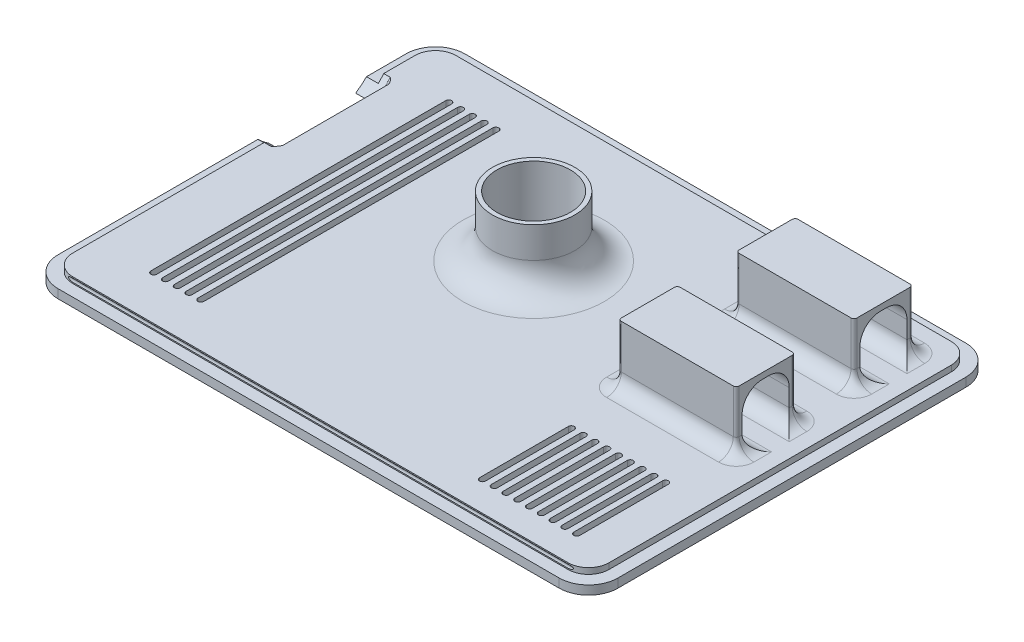
SolidWorks part; units mm, degrees
ref_plane "Front Plane" through (0, 0, 0) normal (0, 0, 1) x (1, 0, 0)
ref_plane "Top Plane" through (0, 0, 0) normal (0, 1, 0) x (1, 0, 0)
ref_plane "Right Plane" through (0, 0, 0) normal (1, 0, 0) x (0, 0, -1)
sketch "Sketch1" plane through (0, 0, 0) normal (0, 1, 0) x (1, 0, 0)
  line L0 (-95.075, -69.075) -> (95.075, -69.075)
  line L7 (95.075, -69.075) -> (95.075, 69.075)
  line L8 (-95.075, 69.075) -> (95.075, 69.075)
  line L9 (-95.075, -69.075) -> (-95.075, 69.075)
  point P0 (0, 69.075)
  point P2 (-95.075, 0)
  dimension "D1" = 138.15
  dimension "D2" = 190.15
extrude "Lid" add sketch "Sketch1" along normal blind 3
sketch "Sketch2" plane through (0, 3, 0) normal (0, 1, 0) x (1, 0, 0)
  line L0 (-91.075, 65.075) -> (-91.075, -65.075)
  line L1 (-91.075, -65.075) -> (91.075, -65.075)
  line L2 (91.075, -65.075) -> (91.075, 65.075)
  line L3 (91.075, 65.075) -> (-91.075, 65.075)
  line L4 (-95.075, 69.075) -> (-95.075, -69.075)
  line L5 (-95.075, -69.075) -> (95.075, -69.075)
  line L6 (95.075, -69.075) -> (95.075, 69.075)
  line L7 (95.075, 69.075) -> (-95.075, 69.075)
  line L8 (-95.075, 69.075) -> (-95.075, -69.075)
  line L9 (-95.075, -69.075) -> (95.075, -69.075)
  line L10 (95.075, -69.075) -> (95.075, 69.075)
  line L11 (95.075, 69.075) -> (-95.075, 69.075)
  dimension "D1" = 0
  dimension "D2" = 4
extrude "Insert" add sketch "Sketch2" along normal blind 2 contours L0 L1 L2 L3
sketch "Sketch3" plane through (0, 5, 0) normal (0, 1, 0) x (1, 0, 0)
  line L1 (41.075, 35.075) -> (81.075, 35.075)
  line L2 (41.075, 35.075) -> (41.075, 55.075)
  line L3 (41.075, 55.075) -> (81.075, 55.075)
  line L4 (91.075, 65.075) -> (-91.075, 65.075)
  line L5 (-91.075, 65.075) -> (-91.075, -65.075)
  line L6 (-91.075, -65.075) -> (91.075, -65.075)
  line L7 (91.075, -65.075) -> (91.075, 65.075)
  line L8 (91.075, 65.075) -> (-91.075, 65.075)
  line L9 (-91.075, 65.075) -> (-91.075, -65.075)
  line L10 (-91.075, -65.075) -> (91.075, -65.075)
  line L11 (91.075, -65.075) -> (91.075, 65.075)
  line L12 (81.075, 35.075) -> (81.075, 55.075)
  line L13 (41.075, 35.075) -> (81.075, 55.075) construction
  line L14 (41.075, 55.075) -> (81.075, 35.075) construction
  line L15 (41.075, 15.075) -> (81.075, 15.075)
  line L16 (41.075, 15.075) -> (41.075, -4.925)
  line L17 (41.075, -4.925) -> (81.075, -4.925)
  line L18 (81.075, 15.075) -> (81.075, -4.925)
  line L19 (41.075, 15.075) -> (81.075, -4.925) construction
  line L20 (41.075, -4.925) -> (81.075, 15.075) construction
  point P2 (61.075, 45.075)
  point P17 (61.075, 5.075)
  dimension "D2" = 10
  dimension "D3" = 50
  dimension "D4" = 10
  dimension "D5" = 30
  dimension "D6" = 50
  dimension "D7" = 70
  dimension "D1" = 0
extrude "Battery Contacts" add sketch "Sketch3" along normal blind 19.9 contours L2 L1 L12 L3 | L16 L15 L18 L17
sketch "Sketch9" plane through (81.075, 0, 0) normal (1, 0, 0) x (0, 0, -1)
  line L0 (-4.925, 5) -> (15.075, 5) construction
  line L1 (53.075, 5) -> (53.075, 15.9)
  line L2 (15.075, 24.9) -> (-4.925, 24.9) construction
  line L3 (53.075, 5) -> (37.075, 5)
  line L4 (35.075, 5) -> (55.075, 5) construction
  line L5 (37.075, 5) -> (37.075, 15.9)
  line L6 (55.075, 24.9) -> (35.075, 24.9) construction
  line L7 (46.075, 22.9) -> (44.075, 22.9)
  line L8 (-4.925, 5) -> (15.075, 5)
  line L9 (15.075, 5) -> (15.075, 24.9)
  line L10 (15.075, 24.9) -> (-4.925, 24.9)
  line L11 (-4.925, 24.9) -> (-4.925, 5)
  line L12 (35.075, 5) -> (55.075, 5)
  line L13 (55.075, 5) -> (55.075, 24.9)
  line L14 (55.075, 24.9) -> (35.075, 24.9)
  line L15 (35.075, 24.9) -> (35.075, 5)
  line L16 (-65.075, 5) -> (65.075, 5) construction
  line L17 (-2.925, 5) -> (13.075, 5)
  line L18 (-2.925, 5) -> (-2.925, 15.9)
  line L19 (4.075, 22.9) -> (6.075, 22.9)
  line L20 (13.075, 5) -> (13.075, 15.9)
  line L21 (25.075, -986.7231) -> (25.075, 49013.2769) construction
  line L22 (53.075, 5) -> (53.075, 15.9)
  arc A0 (-2.925, 15.9) -> (4.075, 22.9) centre (4.075, 15.9) cw
  arc A1 (6.075, 22.9) -> (13.075, 15.9) centre (6.075, 15.9) cw
  arc A2 (53.075, 15.9) -> (46.075, 22.9) centre (46.075, 15.9) ccw
  arc A3 (44.075, 22.9) -> (37.075, 15.9) centre (44.075, 15.9) ccw
  dimension "D1" = 2
  dimension "D2" = 2
  dimension "D3" = 2
  dimension "D4" = 2
  dimension "D5" = 10
extrude "Contact Lighteners" cut sketch "Sketch9" against normal up to next contours A1 L19 A0 L18 L8 L20 | L7 A3 L5 L3 L1 A2 region at (81.075, 13.3646, -45.075) region at (81.075, 13.3646, -5.075)
sketch "Sketch4" plane through (0, 5, 0) normal (0, 1, 0) x (1, 0, 0)
  line L1 (-22.275, 29.625) -> (1.225, 29.625) construction
  line L2 (-22.275, 29.625) -> (-22.275, 6.125) construction
  line L3 (-22.275, 6.125) -> (1.225, 6.125) construction
  line L4 (91.075, 65.075) -> (-91.075, 65.075)
  line L5 (-91.075, 65.075) -> (-91.075, -65.075)
  line L6 (-91.075, -65.075) -> (91.075, -65.075)
  line L7 (91.075, -65.075) -> (91.075, 65.075)
  line L8 (91.075, 65.075) -> (-91.075, 65.075)
  line L9 (-91.075, 65.075) -> (-91.075, -65.075)
  line L10 (-91.075, -65.075) -> (91.075, -65.075)
  line L11 (91.075, -65.075) -> (91.075, 65.075)
  line L12 (1.225, 29.625) -> (1.225, 6.125) construction
  line L13 (-22.275, 29.625) -> (1.225, 6.125) construction
  line L14 (-22.275, 6.125) -> (1.225, 29.625) construction
  line L566 (-10.525, 28.875) -> (-10.525, 6.875) construction
  line L567 (-9.775, 28.875) -> (-9.775, 6.875)
  line L568 (-63.575, 50.075) -> (-63.575, -50.075) construction
  line L569 (-81.075, 50.075) -> (-46.075, 50.075) construction
  line L570 (-81.075, 50.075) -> (-81.075, -50.075) construction
  line L571 (-81.075, -50.075) -> (-46.075, -50.075) construction
  line L572 (-46.075, 50.075) -> (-46.075, -50.075) construction
  line L573 (-62.575, 50.075) -> (-62.575, -50.075)
  line L574 (-64.575, 50.075) -> (-64.575, -50.075)
  line L575 (-59.575, 50.075) -> (-59.575, -50.075) construction
  line L576 (-58.575, 50.075) -> (-58.575, -50.075)
  line L577 (-60.575, 50.075) -> (-60.575, -50.075)
  line L578 (-55.575, 50.075) -> (-55.575, -50.075) construction
  line L579 (-54.575, 50.075) -> (-54.575, -50.075)
  line L580 (-56.575, 50.075) -> (-56.575, -50.075)
  line L581 (-67.575, 50.075) -> (-67.575, -50.075) construction
  line L582 (-11.275, 28.875) -> (-11.275, 6.875)
  line L583 (-7.525, 28.875) -> (-7.525, 6.875) construction
  line L584 (-6.775, 28.875) -> (-6.775, 6.875)
  line L585 (-8.275, 28.875) -> (-8.275, 6.875)
  line L586 (-4.525, 27.9776) -> (-4.525, 7.7724) construction
  line L587 (-3.775, 27.4927) -> (-3.775, 8.2573)
  line L588 (-5.275, 28.3869) -> (-5.275, 7.3631)
  line L589 (-66.575, 50.075) -> (-66.575, -50.075)
  line L590 (-68.575, 50.075) -> (-68.575, -50.075)
  line L591 (-63.575, 50.075) -> (-63.575, -50.075) construction
  line L592 (-62.575, 50.075) -> (-62.575, -50.075)
  line L593 (-64.575, 50.075) -> (-64.575, -50.075)
  line L594 (-71.575, 50.075) -> (-71.575, -50.075) construction
  line L595 (-70.575, 50.075) -> (-70.575, -50.075)
  line L596 (-72.575, 50.075) -> (-72.575, -50.075)
  line L597 (41.075, -4.925) -> (81.075, -4.925) construction
  line L598 (41.075, -55.075) -> (81.075, -55.075) construction
  line L599 (41.075, -55.075) -> (41.075, -24.925) construction
  line L600 (41.075, -24.925) -> (81.075, -24.925) construction
  line L601 (81.075, -55.075) -> (81.075, -24.925) construction
  line L602 (61.075, -24.925) -> (61.075, -55.075) construction
  line L603 (62.075, -24.925) -> (62.075, -55.075)
  line L604 (60.075, -24.925) -> (60.075, -55.075)
  line L605 (65.075, -24.925) -> (65.075, -55.075) construction
  line L606 (66.075, -24.925) -> (66.075, -55.075)
  line L607 (-1.525, 25.429) -> (-1.525, 10.321) construction
  line L608 (-0.775, 24.4324) -> (-0.775, 11.3176)
  line L609 (-2.275, 26.2416) -> (-2.275, 9.5084)
  line L610 (64.075, -24.925) -> (64.075, -55.075)
  line L611 (69.075, -24.925) -> (69.075, -55.075) construction
  line L612 (70.075, -24.925) -> (70.075, -55.075)
  line L613 (68.075, -24.925) -> (68.075, -55.075)
  line L614 (73.075, -24.925) -> (73.075, -55.075) construction
  line L615 (74.075, -24.925) -> (74.075, -55.075)
  line L616 (72.075, -24.925) -> (72.075, -55.075)
  line L617 (77.075, -24.925) -> (77.075, -55.075) construction
  line L618 (78.075, -24.925) -> (78.075, -55.075)
  line L619 (76.075, -24.925) -> (76.075, -55.075)
  line L620 (49.075, -24.925) -> (49.075, -55.075) construction
  line L621 (50.075, -24.925) -> (50.075, -55.075)
  line L622 (48.075, -24.925) -> (48.075, -55.075)
  line L623 (53.075, -24.925) -> (53.075, -55.075) construction
  line L625 (0.725, 21.2662) -> (0.725, 14.4838)
  line L626 (-19.525, 25.429) -> (-19.525, 10.321) construction
  line L627 (-18.775, 26.2416) -> (-18.775, 9.5084)
  line L628 (54.075, -24.925) -> (54.075, -55.075)
  line L629 (52.075, -24.925) -> (52.075, -55.075)
  line L630 (57.075, -24.925) -> (57.075, -55.075) construction
  line L631 (58.075, -24.925) -> (58.075, -55.075)
  line L632 (56.075, -24.925) -> (56.075, -55.075)
  line L634 (-16.525, 27.9776) -> (-16.525, 7.7724) construction
  line L635 (-15.775, 28.3869) -> (-15.775, 7.3631)
  line L636 (-17.275, 27.4927) -> (-17.275, 8.2573)
  line L637 (61.075, -24.925) -> (61.075, -55.075) construction
  line L638 (-13.525, 28.875) -> (-13.525, 6.875) construction
  line L639 (-12.775, 28.875) -> (-12.775, 6.875)
  line L640 (-14.275, 28.875) -> (-14.275, 6.875)
  line L641 (-10.525, 28.875) -> (-10.525, 6.875) construction
  line L642 (62.075, -24.925) -> (62.075, -55.075)
  line L643 (60.075, -24.925) -> (60.075, -55.075)
  line L644 (45.075, -24.925) -> (45.075, -55.075) construction
  line L645 (46.075, -24.925) -> (46.075, -55.075)
  line L646 (44.075, -24.925) -> (44.075, -55.075)
  line L647 (95.075, 69.075) -> (-95.075, 69.075) construction
  line L649 (95.075, -69.075) -> (95.075, 69.075) construction
  line L655 (-9.775, 28.875) -> (-9.775, 6.875)
  line L657 (-11.275, 28.875) -> (-11.275, 6.875)
  line L659 (-21.775, 21.2662) -> (-21.775, 14.4838)
  line L667 (-20.275, 24.4324) -> (-20.275, 11.3176)
  line L1059 (-1.525, 28.875) -> (-1.525, 6.875) construction
  line L1060 (-0.775, 28.875) -> (-0.775, 6.875)
  line L1061 (-2.275, 28.875) -> (-2.275, 6.875)
  line L1062 (-19.525, 28.875) -> (-19.525, 6.875) construction
  line L1063 (-18.775, 28.875) -> (-18.775, 6.875)
  line L1064 (-20.275, 28.875) -> (-20.275, 6.875)
  line L1065 (-16.525, 28.875) -> (-16.525, 6.875) construction
  line L1066 (-15.775, 28.875) -> (-15.775, 6.875)
  line L1067 (-17.275, 28.875) -> (-17.275, 6.875)
  line L1068 (-13.525, 28.875) -> (-13.525, 6.875) construction
  line L1069 (-12.775, 28.875) -> (-12.775, 6.875)
  line L1070 (-14.275, 28.875) -> (-14.275, 6.875)
  line L1071 (-22.525, 28.875) -> (-22.525, 6.875) construction
  line L1072 (-21.775, 28.875) -> (-21.775, 6.875)
  line L1073 (-23.275, 28.875) -> (-23.275, 6.875)
  line L1074 (-4.525, 28.875) -> (-4.525, 6.875) construction
  line L1075 (-3.775, 28.875) -> (-3.775, 6.875)
  line L1076 (-5.275, 28.875) -> (-5.275, 6.875)
  line L1077 (-7.525, 28.875) -> (-7.525, 6.875) construction
  line L1078 (-6.775, 28.875) -> (-6.775, 6.875)
  line L1079 (-8.275, 28.875) -> (-8.275, 6.875)
  line L1080 (1.475, 28.875) -> (1.475, 6.875) construction
  line L1081 (2.225, 28.875) -> (2.225, 6.875)
  line L1082 (0.725, 28.875) -> (0.725, 6.875)
  line L1083 (-1.525, 28.875) -> (-1.525, 6.875) construction
  line L1084 (-0.775, 28.875) -> (-0.775, 6.875)
  line L1085 (-2.275, 28.875) -> (-2.275, 6.875)
  line L1086 (-19.525, 28.875) -> (-19.525, 6.875) construction
  line L1087 (-18.775, 28.875) -> (-18.775, 6.875)
  line L1088 (-20.275, 28.875) -> (-20.275, 6.875)
  line L1089 (-16.525, 28.875) -> (-16.525, 6.875) construction
  line L1090 (-15.775, 28.875) -> (-15.775, 6.875)
  line L1091 (-17.275, 28.875) -> (-17.275, 6.875)
  line L1092 (-13.525, 28.875) -> (-13.525, 6.875) construction
  line L1093 (-12.775, 28.875) -> (-12.775, 6.875)
  line L1094 (-14.275, 28.875) -> (-14.275, 6.875)
  line L1095 (-22.525, 28.875) -> (-22.525, 6.875) construction
  line L1096 (-21.775, 28.875) -> (-21.775, 6.875)
  line L1097 (-23.275, 28.875) -> (-23.275, 6.875)
  line L1098 (-4.525, 28.875) -> (-4.525, 6.875) construction
  line L1099 (-3.775, 28.875) -> (-3.775, 6.875)
  line L1100 (-5.275, 28.875) -> (-5.275, 6.875)
  line L1101 (-7.525, 28.875) -> (-7.525, 6.875) construction
  line L1102 (-6.775, 28.875) -> (-6.775, 6.875)
  line L1103 (-8.275, 28.875) -> (-8.275, 6.875)
  line L1104 (1.475, 28.875) -> (1.475, 6.875) construction
  line L1105 (2.225, 28.875) -> (2.225, 6.875)
  line L1106 (0.725, 28.875) -> (0.725, 6.875)
  circle A12 centre (-10.525, 17.875) radius 11.75
  arc A13 (-9.775, 28.875) -> (-11.275, 28.875) centre (-10.525, 28.875) ccw
  arc A14 (-11.275, 6.875) -> (-9.775, 6.875) centre (-10.525, 6.875) ccw
  arc A15 (-6.775, 28.875) -> (-6.7882, 29.015) centre (-7.525, 28.875) ccw
  arc A16 (-8.275, 6.875) -> (-8.0887, 6.3803) centre (-7.525, 6.875) ccw
  arc A27 (-12.775, 28.875) -> (-12.9613, 29.3697) centre (-13.525, 28.875) ccw
  arc A28 (-14.275, 6.875) -> (-14.2618, 6.735) centre (-13.525, 6.875) ccw
  arc A29 (-9.775, 28.875) -> (-11.275, 28.875) centre (-10.525, 28.875) ccw
  arc A30 (-11.275, 6.875) -> (-9.775, 6.875) centre (-10.525, 6.875) ccw
  arc A33 (-62.575, 50.075) -> (-64.575, 50.075) centre (-63.575, 50.075) ccw
  arc A34 (-64.575, -50.075) -> (-62.575, -50.075) centre (-63.575, -50.075) ccw
  arc A35 (-58.575, 50.075) -> (-60.575, 50.075) centre (-59.575, 50.075) ccw
  arc A36 (-60.575, -50.075) -> (-58.575, -50.075) centre (-59.575, -50.075) ccw
  arc A37 (-54.575, 50.075) -> (-56.575, 50.075) centre (-55.575, 50.075) ccw
  arc A38 (-56.575, -50.075) -> (-54.575, -50.075) centre (-55.575, -50.075) ccw
  arc A39 (-14.2618, 29.015) -> (-14.275, 28.875) centre (-13.525, 28.875) ccw
  arc A40 (-66.575, 50.075) -> (-68.575, 50.075) centre (-67.575, 50.075) ccw
  arc A41 (-68.575, -50.075) -> (-66.575, -50.075) centre (-67.575, -50.075) ccw
  arc A42 (-12.9613, 6.3803) -> (-12.775, 6.875) centre (-13.525, 6.875) ccw
  arc A43 (-62.575, 50.075) -> (-64.575, 50.075) centre (-63.575, 50.075) ccw
  arc A44 (-64.575, -50.075) -> (-62.575, -50.075) centre (-63.575, -50.075) ccw
  arc A45 (-70.575, 50.075) -> (-72.575, 50.075) centre (-71.575, 50.075) ccw
  arc A46 (-72.575, -50.075) -> (-70.575, -50.075) centre (-71.575, -50.075) ccw
  arc A47 (62.075, -24.925) -> (60.075, -24.925) centre (61.075, -24.925) ccw
  arc A48 (60.075, -55.075) -> (62.075, -55.075) centre (61.075, -55.075) ccw
  arc A49 (-6.7882, 6.735) -> (-6.775, 6.875) centre (-7.525, 6.875) ccw
  arc A50 (66.075, -24.925) -> (64.075, -24.925) centre (65.075, -24.925) ccw
  arc A51 (64.075, -55.075) -> (66.075, -55.075) centre (65.075, -55.075) ccw
  arc A52 (-8.0887, 29.3697) -> (-8.275, 28.875) centre (-7.525, 28.875) ccw
  arc A53 (70.075, -24.925) -> (68.075, -24.925) centre (69.075, -24.925) ccw
  arc A54 (68.075, -55.075) -> (70.075, -55.075) centre (69.075, -55.075) ccw
  arc A55 (74.075, -24.925) -> (72.075, -24.925) centre (73.075, -24.925) ccw
  arc A56 (72.075, -55.075) -> (74.075, -55.075) centre (73.075, -55.075) ccw
  arc A57 (78.075, -24.925) -> (76.075, -24.925) centre (77.075, -24.925) ccw
  arc A58 (76.075, -55.075) -> (78.075, -55.075) centre (77.075, -55.075) ccw
  arc A59 (50.075, -24.925) -> (48.075, -24.925) centre (49.075, -24.925) ccw
  arc A60 (48.075, -55.075) -> (50.075, -55.075) centre (49.075, -55.075) ccw
  arc A61 (54.075, -24.925) -> (52.075, -24.925) centre (53.075, -24.925) ccw
  arc A62 (52.075, -55.075) -> (54.075, -55.075) centre (53.075, -55.075) ccw
  arc A63 (58.075, -24.925) -> (56.075, -24.925) centre (57.075, -24.925) ccw
  arc A64 (56.075, -55.075) -> (58.075, -55.075) centre (57.075, -55.075) ccw
  arc A65 (62.075, -24.925) -> (60.075, -24.925) centre (61.075, -24.925) ccw
  arc A66 (60.075, -55.075) -> (62.075, -55.075) centre (61.075, -55.075) ccw
  arc A67 (46.075, -24.925) -> (44.075, -24.925) centre (45.075, -24.925) ccw
  arc A68 (44.075, -55.075) -> (46.075, -55.075) centre (45.075, -55.075) ccw
  arc A293 (-0.775, 28.875) -> (-2.275, 28.875) centre (-1.525, 28.875) ccw
  arc A294 (-2.275, 6.875) -> (-0.775, 6.875) centre (-1.525, 6.875) ccw
  arc A295 (-18.775, 28.875) -> (-20.275, 28.875) centre (-19.525, 28.875) ccw
  arc A296 (-20.275, 6.875) -> (-18.775, 6.875) centre (-19.525, 6.875) ccw
  arc A297 (-15.775, 28.875) -> (-17.275, 28.875) centre (-16.525, 28.875) ccw
  arc A298 (-17.275, 6.875) -> (-15.775, 6.875) centre (-16.525, 6.875) ccw
  arc A299 (-12.775, 28.875) -> (-14.275, 28.875) centre (-13.525, 28.875) ccw
  arc A300 (-14.275, 6.875) -> (-12.775, 6.875) centre (-13.525, 6.875) ccw
  arc A301 (-21.775, 28.875) -> (-23.275, 28.875) centre (-22.525, 28.875) ccw
  arc A302 (-23.275, 6.875) -> (-21.775, 6.875) centre (-22.525, 6.875) ccw
  arc A303 (-3.775, 28.875) -> (-5.275, 28.875) centre (-4.525, 28.875) ccw
  arc A304 (-5.275, 6.875) -> (-3.775, 6.875) centre (-4.525, 6.875) ccw
  arc A305 (-6.775, 28.875) -> (-8.275, 28.875) centre (-7.525, 28.875) ccw
  arc A306 (-8.275, 6.875) -> (-6.775, 6.875) centre (-7.525, 6.875) ccw
  arc A307 (2.225, 28.875) -> (0.725, 28.875) centre (1.475, 28.875) ccw
  arc A308 (0.725, 6.875) -> (2.225, 6.875) centre (1.475, 6.875) ccw
  point P2 (-10.525, 17.875)
  point P21 (-10.525, 17.875)
  point P30 (-5.675, 22.825)
  point P31 (-17.675, 22.825)
  point P38 (-2.675, 22.825)
  point P45 (0.325, 22.825)
  point P52 (3.325, 22.825)
  point P59 (-17.675, 22.825)
  point P60 (-63.575, 0)
  point P62 (-14.675, 22.825)
  point P66 (-14.675, 22.825)
  point P73 (-11.675, 22.825)
  point P80 (-10.525, 17.875)
  point P87 (-20.675, 22.825)
  point P91 (0.325, 22.825)
  point P99 (-59.575, 0)
  point P104 (-11.675, 22.825)
  point P109 (-55.575, 0)
  point P114 (-20.675, 22.825)
  point P121 (-67.575, 0)
  point P126 (-2.675, 22.825)
  point P129 (-63.575, 0)
  point P133 (-5.675, 22.825)
  point P137 (-71.575, 0)
  point P142 (3.325, 22.825)
  point P151 (61.075, -40)
  point P160 (65.075, -40)
  point P167 (69.075, -40)
  point P174 (73.075, -40)
  point P181 (77.075, -40)
  point P188 (49.075, -40)
  point P195 (53.075, -40)
  point P202 (57.075, -40)
  point P209 (61.075, -40)
  point P216 (45.075, -40)
  point P825 (0.325, 22.825)
  point P832 (-17.675, 22.825)
  point P839 (-14.675, 22.825)
  point P846 (-11.675, 22.825)
  point P853 (-20.675, 22.825)
  point P860 (-2.675, 22.825)
  point P867 (-5.675, 22.825)
  point P874 (3.325, 22.825)
  point P881 (0.325, 22.825)
  point P888 (-17.675, 22.825)
  point P895 (-14.675, 22.825)
  point P902 (-11.675, 22.825)
  point P909 (-20.675, 22.825)
  point P916 (-2.675, 22.825)
  point P923 (-5.675, 22.825)
  point P930 (3.325, 22.825)
  point P937 (0.325, 22.825)
  point P944 (-17.675, 22.825)
  point P951 (-14.675, 22.825)
  point P958 (-11.675, 22.825)
  point P965 (-20.675, 22.825)
  point P972 (-2.675, 22.825)
  point P979 (-5.675, 22.825)
  point P986 (3.325, 22.825)
  point P993 (0.325, 22.825)
  point P1000 (-17.675, 22.825)
  point P1007 (-14.675, 22.825)
  point P1014 (-11.675, 22.825)
  point P1021 (-20.675, 22.825)
  point P1028 (-2.675, 22.825)
  point P1035 (-5.675, 22.825)
  point P1042 (3.325, 22.825)
  point P1049 (0.325, 22.825)
  point P1056 (-17.675, 22.825)
  point P1063 (-14.675, 22.825)
  point P1070 (-11.675, 22.825)
  point P1077 (-20.675, 22.825)
  point P1084 (-2.675, 22.825)
  point P1091 (-5.675, 22.825)
  point P1098 (3.325, 22.825)
  point P1105 (0.325, 22.825)
  point P1112 (-17.675, 22.825)
  point P1119 (-14.675, 22.825)
  point P1126 (-11.675, 22.825)
  point P1133 (-20.675, 22.825)
  point P1140 (-2.675, 22.825)
  point P1147 (-5.675, 22.825)
  point P1154 (3.325, 22.825)
  point P1161 (0.325, 22.825)
  point P1168 (-17.675, 22.825)
  point P1175 (-14.675, 22.825)
  point P1182 (-11.675, 22.825)
  point P1189 (-20.675, 22.825)
  point P1196 (-2.675, 22.825)
  point P1203 (-5.675, 22.825)
  point P1210 (3.325, 22.825)
  point P1217 (-1.525, 17.875)
  point P1224 (-19.525, 17.875)
  point P1231 (-16.525, 17.875)
  point P1238 (-13.525, 17.875)
  point P1245 (-22.525, 17.875)
  point P1252 (-4.525, 17.875)
  point P1259 (-7.525, 17.875)
  point P1266 (1.475, 17.875)
  point P1273 (-1.525, 17.875)
  point P1280 (-19.525, 17.875)
  point P1287 (-16.525, 17.875)
  point P1294 (-13.525, 17.875)
  point P1301 (-22.525, 17.875)
  point P1308 (-4.525, 17.875)
  point P1315 (-7.525, 17.875)
  point P1322 (1.475, 17.875)
  point P1329 (-1.525, 17.875)
  point P1336 (-19.525, 17.875)
  point P1343 (-16.525, 17.875)
  point P1350 (-13.525, 17.875)
  point P1357 (-22.525, 17.875)
  point P1364 (-4.525, 17.875)
  point P1371 (-7.525, 17.875)
  point P1378 (1.475, 17.875)
  point P1385 (-1.525, 17.875)
  point P1392 (-19.525, 17.875)
  point P1399 (-16.525, 17.875)
  point P1406 (-13.525, 17.875)
  point P1413 (-22.525, 17.875)
  point P1420 (-4.525, 17.875)
  point P1427 (-7.525, 17.875)
  point P1434 (1.475, 17.875)
  point P1441 (-1.525, 17.875)
  point P1448 (-19.525, 17.875)
  point P1455 (-16.525, 17.875)
  point P1462 (-13.525, 17.875)
  point P1469 (-22.525, 17.875)
  point P1476 (-4.525, 17.875)
  point P1483 (-7.525, 17.875)
  point P1490 (1.475, 17.875)
  point P1497 (-1.525, 17.875)
  point P1504 (-19.525, 17.875)
  point P1511 (-16.525, 17.875)
  point P1518 (-13.525, 17.875)
  point P1525 (-22.525, 17.875)
  point P1532 (-4.525, 17.875)
  point P1539 (-7.525, 17.875)
  point P1546 (1.475, 17.875)
  point P1553 (-1.525, 17.875)
  point P1560 (-19.525, 17.875)
  point P1567 (-16.525, 17.875)
  point P1574 (-13.525, 17.875)
  point P1581 (-22.525, 17.875)
  point P1588 (-4.525, 17.875)
  point P1595 (-7.525, 17.875)
  point P1602 (1.475, 17.875)
  point P1609 (-1.525, 17.875)
  point P1616 (-19.525, 17.875)
  point P1623 (-16.525, 17.875)
  point P1630 (-13.525, 17.875)
  point P1637 (-22.525, 17.875)
  point P1644 (-4.525, 17.875)
  point P1651 (-7.525, 17.875)
  point P1658 (1.475, 17.875)
  point P1665 (-1.525, 17.875)
  point P1672 (-19.525, 17.875)
  point P1679 (-16.525, 17.875)
  point P1686 (-13.525, 17.875)
  point P1693 (-22.525, 17.875)
  point P1700 (-4.525, 17.875)
  point P1707 (-7.525, 17.875)
  point P1714 (1.475, 17.875)
  dimension "D3" = 23.5
  dimension "D4" = 51.2
  dimension "D5" = 1.5
  dimension "D6" = 2
  dimension "D7" = 5
  dimension "D8" = 1.5
  dimension "D9" = 1.5
  dimension "D10" = 15
  dimension "D11" = 15
  dimension "D12" = 10
  dimension "D13" = 45
  dimension "D14" = 2
  dimension "D15" = 2
  dimension "D16" = 3
  dimension "D17" = 2
  dimension "D18" = 10
  dimension "D19" = 10
  dimension "D20" = 20
  dimension "D21" = 50
  dimension "D22" = 2
  dimension "D23" = 2
  dimension "D24" = 5
  dimension "D25" = 2
  dimension "D26" = 105.6
  dimension "D1" = 0
extrude "Vent Holes" cut sketch "Sketch4" against normal through all contours L659 A12 | L627 A12 L667 | L635 A12 L636 | A12 A42 L639 A27 A39 L640 A28 | A14 L567 A13 L582 | A12 A52 L585 A16 A49 L584 A15 | L588 A12 L587 | L609 A12 L608 | L625 A12 | L645 A68 L646 A67 | L621 A60 L622 A59 | L628 A62 L629 A61 | L631 A64 L632 A63 | L604 A48 L603 A47 | L606 A51 L610 A50 | L612 A54 L613 A53 | L615 A56 L616 A55 | L618 A58 L619 A57 | L595 A46 L596 A45 | L589 A41 L590 A40 | L592 A44 L593 A43 | L576 A36 L577 A35 | L579 A38 L580 A37 region at (-10.525, 5, -17.875) region at (-7.5281, 5, -17.875) region at (-13.5219, 5, -17.875) region at (-4.5361, 5, -17.875) region at (-16.5139, 5, -17.875) region at (-1.5549, 5, -17.875) region at (-19.4951, 5, -17.875) region at (0.9254, 5, -17.875) region at (-21.9754, 5, -17.875)
fillet "Fillet1" radius 10 4 edges at (95.075, 1.5, -69.075) (95.075, 1.5, 69.075) (-95.075, 1.5, -69.075) (-95.075, 1.5, 69.075)
fillet "Fillet2" radius 6.95 4 edges at (-91.075, 4, -65.075) (91.075, 4, -65.075) (91.075, 4, 65.075) (-91.075, 4, 65.075)
sketch "Sketch5" plane through (91.075, 0, 0) normal (1, 0, 0) x (0, 0, -1)
  line L0 (-65.075, 3) -> (-65.075, 5) construction
  line L1 (-65.075, 4.6) -> (-65.075, 3.4)
  line L2 (65.075, 5) -> (65.075, 3) construction
  line L3 (65.075, 5) -> (58.125, 5) construction
  line L4 (65.075, 4.6) -> (65.075, 3.4)
  arc A0 (-65.075, 4.6) -> (-65.075, 3.4) centre (-65.875, 4) cw
  arc A1 (65.075, 4.6) -> (65.075, 3.4) centre (65.875, 4) ccw
  dimension "D3" = 1
  dimension "D6" = 1
  dimension "D1" = 0.4
  dimension "D2" = 0.4
  dimension "D4" = 0.4
  dimension "D5" = 1.2
extrude "Snap Groove" cut sketch "Sketch5" against normal through all
sketch "Sketch6" plane through (0, 5, 0) normal (0, 1, 0) x (1, 0, 0)
  line L4 (84.125, 65.075) -> (-84.125, 65.075)
  line L5 (-91.075, 58.125) -> (-91.075, -58.125)
  line L6 (-84.125, -65.075) -> (84.125, -65.075)
  line L7 (91.075, -58.125) -> (91.075, 58.125)
  line L8 (84.125, 65.075) -> (-84.125, 65.075)
  line L9 (-91.075, 58.125) -> (-91.075, -58.125)
  line L10 (-84.125, -65.075) -> (84.125, -65.075)
  line L11 (91.075, -58.125) -> (91.075, 58.125)
  circle A0 centre (-10.525, 17.875) radius 12.5
  circle A1 centre (-10.525, 17.875) radius 14
  arc A4 (-84.125, 65.075) -> (-91.075, 58.125) centre (-84.125, 58.125) ccw
  arc A5 (-91.075, -58.125) -> (-84.125, -65.075) centre (-84.125, -58.125) ccw
  arc A6 (84.125, -65.075) -> (91.075, -58.125) centre (84.125, -58.125) ccw
  arc A7 (91.075, 58.125) -> (84.125, 65.075) centre (84.125, 58.125) ccw
  arc A8 (-84.125, 65.075) -> (-91.075, 58.125) centre (-84.125, 58.125) ccw
  arc A9 (-91.075, -58.125) -> (-84.125, -65.075) centre (-84.125, -58.125) ccw
  arc A10 (84.125, -65.075) -> (91.075, -58.125) centre (84.125, -58.125) ccw
  arc A11 (91.075, 58.125) -> (84.125, 65.075) centre (84.125, 58.125) ccw
  dimension "D2" = 28
  dimension "D3" = 1.5
  dimension "D1" = 0
extrude "Cooling Guide" add sketch "Sketch6" along normal blind 20.5 contours A1 A0 region at (-24.129, 5, -17.875)
fillet "Fillet5" radius 10 1 edges at (-10.525, 5, -3.875)
sketch "Sketch8" plane through (-95.075, 0, 0) normal (-1, 0, 0) x (0, 0, 1)
  line L0 (-59.075, 3) -> (-59.075, 48) construction
  line L2 (-59.075, 3) -> (59.075, 3) construction
  line L5 (-27.225, 48) -> (-27.225, 21.9) construction
  circle A0 centre (-27.225, 21.9) radius 26.4
  dimension "D4" = 52.8
  dimension "D1" = 45
  dimension "D2" = 31.85
  dimension "D3" = 26.1
extrude "EDoF Insert" cut sketch "Sketch8" against normal blind 8
fillet "Fillet6" radius 1.8 2 edges at (-87.075, 2.3033, -9.5352) (-87.075, 2.3033, -44.9148) conic radius 7
fillet "Fillet7" radius 1 8 edges at (81.075, 14.95, -55.075) (81.075, 14.95, -35.075) (41.075, 14.95, -35.075) (41.075, 14.95, -55.075) (41.075, 14.95, -15.075) (41.075, 14.95, 4.925) (81.075, 14.95, 4.925) (81.075, 14.95, -15.075)
fillet "Fillet8" radius 5 24 edges at (41.075, 5, 3.425) (41.3679, 5, 4.6321) (81.075, 5, 3.425) (80.7821, 5, 4.6321) (41.075, 5, -36.575) (41.3679, 5, -35.3679) (81.075, 5, -36.575) (80.7821, 5, -35.3679) (41.075, 5, -53.575) (41.3679, 5, -54.7821) (81.075, 5, -53.575) (80.7821, 5, -54.7821) (41.075, 5, -13.575) (41.3679, 5, -14.7821) (81.075, 5, -13.575) (80.7821, 5, -14.7821) (61.075, 5, 4.925) (61.075, 5, -13.075) (61.075, 5, -35.075) (61.075, 5, -53.075) (61.075, 5, -37.075) (61.075, 5, 2.925) (61.075, 5, -55.075) (61.075, 5, -15.075)
